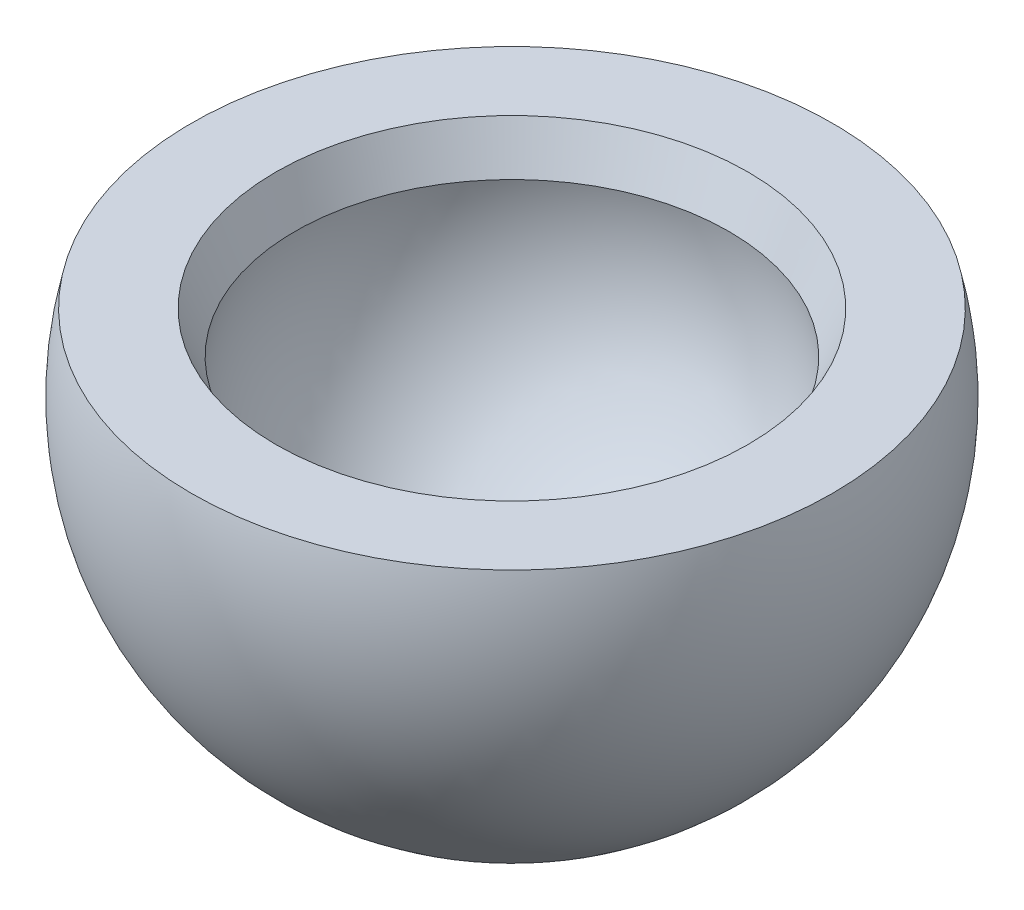
SolidWorks part; units mm, degrees
material "PA Type 6"
ref_plane "Front Plane" through (0, 0, 0) normal (0, 0, 1) x (1, 0, 0)
ref_plane "Top Plane" through (0, 0, 0) normal (0, 1, 0) x (1, 0, 0)
ref_plane "Right Plane" through (0, 0, 0) normal (1, 0, 0) x (0, 0, -1)
sketch "Sketch1" plane through (0, 0, 0) normal (0, 0, 1) x (1, 0, 0)
  line L0 (0, 38.1) -> (0, -38.1) construction
  line L1 (0, 38.1) -> (0, -38.1)
  arc A0 (0, -38.1) -> (0, 38.1) centre (0, 0) ccw
  dimension "D1" = 76.2
revolve "Revolve1" add sketch "Sketch1" angle 360 about L0
ref_plane "Plane1" through (0, 8.89, 0) normal (0, 1, 0) x (-1, 0, 0)
sketch "Sketch2" plane through (0, 8.89, 0) normal (0, 1, 0) x (-1, 0, 0)
  circle A0 centre (0, 0) radius 37.8269
  dimension "D1" = 75.6539
extrude "Extrude1" cut sketch "Sketch2" along normal blind 50.8
sketch "Sketch3" plane through (0, 0, 0) normal (0, 1, 0) x (1, 0, 0)
  line L0 (0, 25.4) -> (0, -25.4)
  arc A0 (0, -25.4) -> (0, 25.4) centre (0, 0) ccw
  circle A1 centre (0, 0) radius 38.1 construction
  dimension "D1" = 12.7
revolve "Cut-Revolve1" cut sketch "Sketch3" angle 360 about L0
chamfer "Chamfer1" distance 4.4901 angle 45 1 edges at (0, 8.89, 23.7934) first distance on face at (0, 8.89, 23.7934)
ref_plane "Plane2" through (0, -16.51, 0) normal (0, 1, 0) x (-1, 0, 0)
